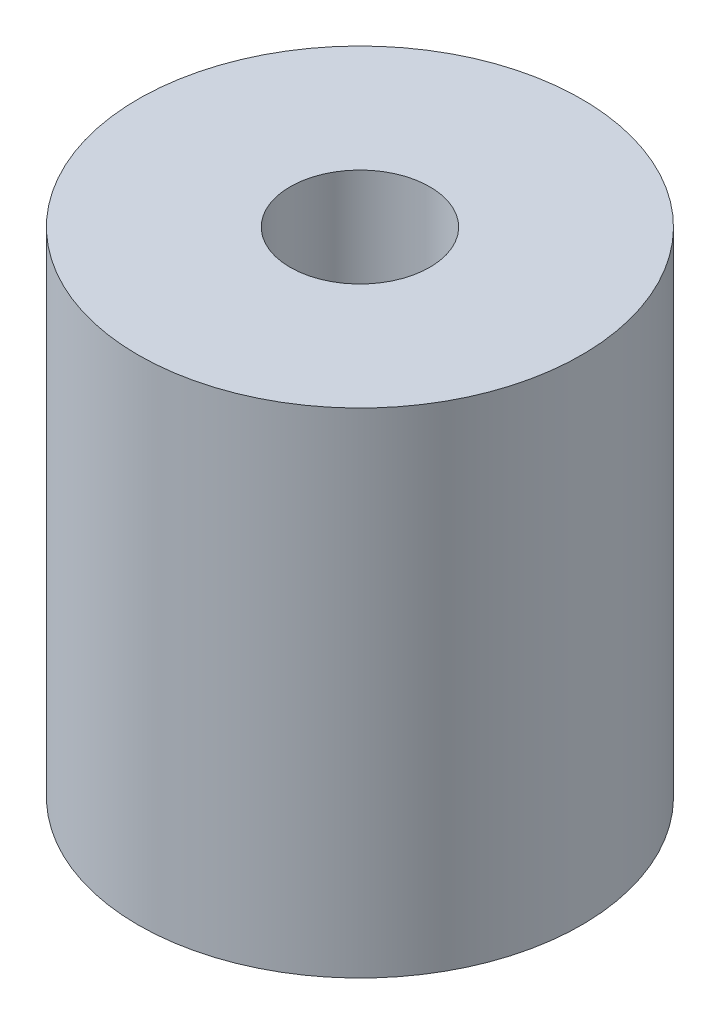
SolidWorks part; units mm, degrees
ref_plane "Front Plane" through (0, 0, 0) normal (0, 0, 1) x (1, 0, 0)
ref_plane "Top Plane" through (0, 0, 0) normal (0, 1, 0) x (1, 0, 0)
ref_plane "Right Plane" through (0, 0, 0) normal (1, 0, 0) x (0, 0, -1)
sketch "Sketch1" plane through (0, 0, 0) normal (0, 1, 0) x (1, 0, 0)
  circle A0 centre (0, 0) radius 5
  circle A1 centre (0, 0) radius 1.575
  dimension "D1" = 10
  dimension "D2" = 3.15
extrude "Boss-Extrude1" add sketch "Sketch1" along normal blind 11.132
sketch "Sketch2" plane through (0, 11.132, 0) normal (0, 1, 0) x (1, 0, 0)
  circle A0 centre (0, 0) radius 1.925
  dimension "D1" = 3.85
extrude "Cut-Extrude1" [suppressed] cut sketch "Sketch2" against normal blind 4
equation "\"D1@Boss-Extrude1\"=\"sheetThickness\"*2+0.5*\"ballBearDiam\""
equation "\"largeBearOD\"= 21mm"
equation "\"largeBearID\" = 15mm"
equation "\"largeBearOTight\"= 0.127mm'calibrate - hold onto gears"
equation "\"largeBearITight\"= 0mm'calibrate - hold onto eccentric nut"
equation "\"largeBearFlangeDiam\" = 22.5mm"
equation "\"largeBearFlangeWidth\" = 0.8mm"
equation "\"smallBearOD\"= 15mm"
equation "\"smallBearOTight\"= 0mm'calibrate - hold onto bottom of gearbox"
equation "\"smallBearOLoose\"= 0mm'calibrate - able to take off topHat"
equation "\"smallBearID\" = 10mm"
equation "\"smallBearITight\" = 0mm'hold onto "
equation "\"pinCircleDiam\"= 75mm"
equation "\"pinDiam\"= 6mm"
equation "\"sheetThickness\"= 0.1875in"
equation "\"ballBearDiam\"= 3.214mm"
equation "\"thrustBearingThickness\"= 5mm'measure this irl and change"
equation "\"thrustBearingID\"= 0mm'measure this irl and change"
equation "\"thrustBearingOD\"= 0mm'measure this irl and change"
equation "\"eccentricity\" = 1mm"
